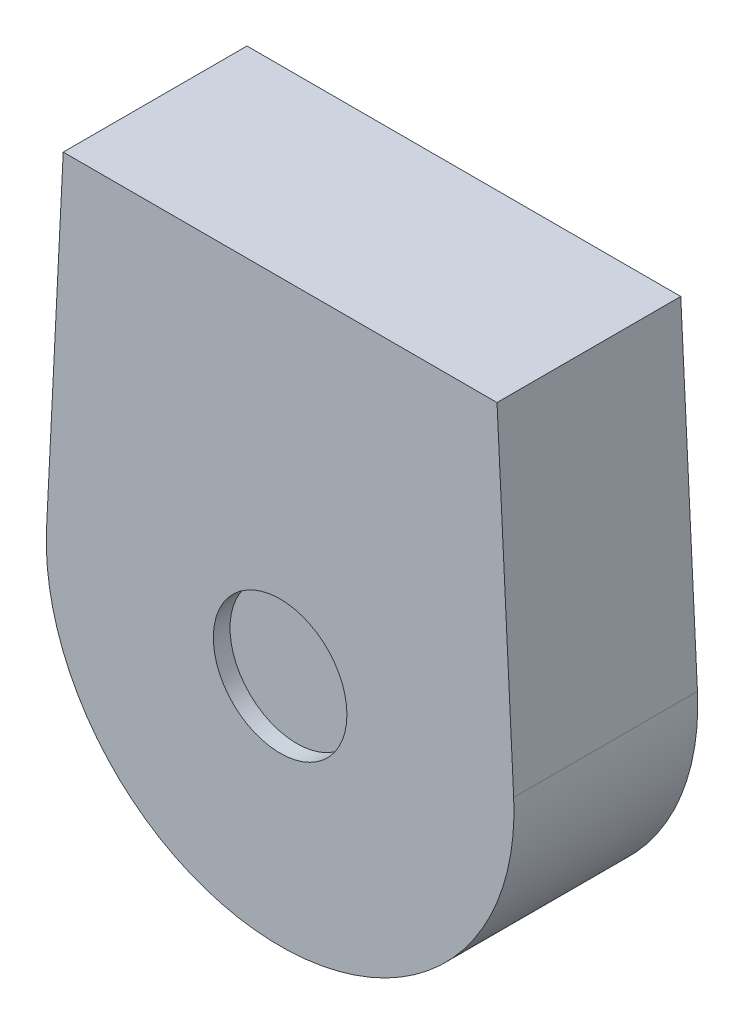
SolidWorks part; units mm, degrees
ref_plane "Front Plane" through (0, 0, 0) normal (0, 0, 1) x (1, 0, 0)
ref_plane "Top Plane" through (0, 0, 0) normal (0, 1, 0) x (1, 0, 0)
ref_plane "Right Plane" through (0, 0, 0) normal (1, 0, 0) x (0, 0, -1)
sketch "Sketch2" plane through (0, 0, 0) normal (0, 0, 1) x (1, 0, 0)
  line L0 (-35.5156, 1.7758) -> (-32.9788, 52.5124)
  line L1 (32.9788, 52.5124) -> (35.5156, 1.7758)
  line L3 (-32.9788, 52.5124) -> (32.9788, 52.5124)
  arc A0 (-35.5156, 1.7758) -> (35.5156, 1.7758) centre (0, 0) ccw
  dimension "D1" = 35.56
  dimension "D2" = 50.8
extrude "Boss-Extrude1" add sketch "Sketch2" along normal blind 13.97 and the other way blind 13.97
sketch "Sketch3" plane through (0, 0, 13.97) normal (0, 0, 1) x (1, 0, 0)
  line L0 (0, 220.9537) -> (0, -35.56) construction
  line L1 (-35.56, 0) -> (35.56, 0) construction
  arc A1 (-35.5156, 1.7758) -> (35.5156, 1.7758) centre (0, 0) ccw construction
  circle A2 centre (0, 0) radius 10.16
  point P3 (0, 92.6969)
  dimension "D1" = 20.32
extrude "Cut-Extrude1" cut sketch "Sketch3" against normal blind 2.54
sketch "Sketch4" plane through (-35.5156, 1.7758, 0) normal (-0.9988, 0.0499, 0) x (0, 0, 1)
  line L0 (0, -35.56) -> (0, 50.8) construction
  line L1 (10.033, 45.7897) -> (-10.033, 45.7897)
  line L2 (10.033, 45.7897) -> (10.033, 4.6417)
  line L3 (10.033, 4.6417) -> (-10.033, 4.6417)
  line L4 (-10.033, 45.7897) -> (-10.033, 4.6417)
  line L5 (10.033, 45.7897) -> (-10.033, 4.6417) construction
  line L6 (10.033, 4.6417) -> (-10.033, 45.7897) construction
  line L7 (-13.97, -35.56) -> (13.97, -35.56) construction
  line L8 (-13.97, 50.8) -> (13.97, 50.8) construction
  point P0 (0, 25.2157)
  dimension "D1" = 20.066
  dimension "D2" = 41.148
extrude "Cut-Extrude2" [suppressed] cut sketch "Sketch4" against normal blind 26.924
sketch "Sketch5" plane through (0, 0, -13.97) normal (0, 0, -1) x (-1, 0, 0)
  line L1 (18.4456, -6.9601) -> (10.725, -6.9601)
  line L2 (18.4456, -6.9601) -> (18.4456, 4.7313)
  line L3 (18.4456, 4.7313) -> (10.725, 4.7313)
  line L4 (10.725, -6.9601) -> (10.725, 4.7313)
extrude "Cut-Extrude3" cut sketch "Sketch5" against normal blind 22.098
